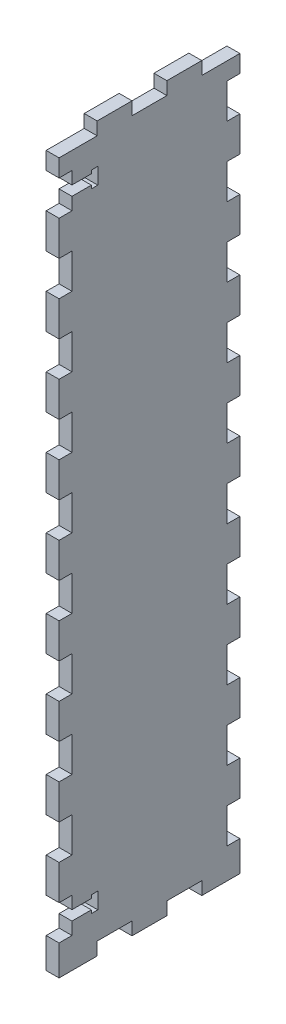
SolidWorks part; units mm, degrees
ref_plane "Front Plane" through (0, 0, 0) normal (0, 0, 1) x (1, 0, 0)
ref_plane "Top Plane" through (0, 0, 0) normal (0, 1, 0) x (1, 0, 0)
ref_plane "Right Plane" through (0, 0, 0) normal (1, 0, 0) x (0, 0, -1)
sketch "Sketch1" plane through (0, 0, 0) normal (1, 0, 0) x (0, 0, -1)
  line L0 (6.35, 355.6) -> (6.35, 349.25) construction
  line L1 (0, 0) -> (88.9, 0) construction
  line L2 (0, 0) -> (0, 6.35) construction
  line L3 (6.35, 355.6) -> (76.2, 355.6) construction
  line L4 (88.9, 0) -> (88.9, 6.35) construction
  line L5 (0, 6.35) -> (88.9, 6.35) construction
  line L6 (6.35, 349.25) -> (88.9, 349.25) construction
  line L7 (82.55, 355.6) -> (82.55, 338.1375) construction
  line L8 (0, 6.35) -> (0, 0)
  line L9 (0, 0) -> (6.35, 0)
  line L10 (6.35, 0) -> (18.7325, 0)
  line L11 (18.7325, 0) -> (18.7325, 6.35)
  line L12 (18.7325, 6.35) -> (35.8775, 6.35)
  line L13 (35.8775, 6.35) -> (35.8775, 0)
  line L14 (35.8775, 0) -> (53.0225, 0)
  line L15 (53.0225, 0) -> (53.0225, 6.35)
  line L16 (53.0225, 6.35) -> (70.1675, 6.35)
  line L17 (70.1675, 6.35) -> (70.1675, 0)
  line L18 (70.1675, 0) -> (82.55, 0)
  line L19 (82.55, 0) -> (88.9, 0)
  line L20 (88.9, 0) -> (88.9, 6.35)
  line L21 (6.35, 12.3825) -> (6.35, 0) construction
  line L22 (0, 0) -> (0, 349.25) construction
  line L23 (0, 6.35) -> (0, 14.9225)
  line L24 (0, 49.2125) -> (6.35, 49.2125)
  line L25 (6.35, 49.2125) -> (6.35, 66.3575)
  line L26 (6.35, 66.3575) -> (0, 66.3575)
  line L27 (0, 66.3575) -> (0, 83.5025)
  line L28 (0, 83.5025) -> (6.35, 83.5025)
  line L29 (6.35, 83.5025) -> (6.35, 100.6475)
  line L30 (6.35, 100.6475) -> (0, 100.6475)
  line L31 (0, 100.6475) -> (0, 117.7925)
  line L32 (0, 117.7925) -> (6.35, 117.7925)
  line L33 (6.35, 117.7925) -> (6.35, 134.9375)
  line L34 (6.35, 134.9375) -> (0, 134.9375)
  line L35 (0, 134.9375) -> (0, 152.0825)
  line L36 (0, 152.0825) -> (6.35, 152.0825)
  line L37 (6.35, 152.0825) -> (6.35, 169.2275)
  line L38 (6.35, 169.2275) -> (0, 169.2275)
  line L39 (0, 169.2275) -> (0, 186.3725)
  line L40 (0, 186.3725) -> (6.35, 186.3725)
  line L41 (6.35, 186.3725) -> (6.35, 203.5175)
  line L42 (6.35, 203.5175) -> (0, 203.5175)
  line L43 (0, 203.5175) -> (0, 220.6625)
  line L44 (0, 220.6625) -> (6.35, 220.6625)
  line L45 (6.35, 220.6625) -> (6.35, 237.8075)
  line L46 (6.35, 237.8075) -> (0, 237.8075)
  line L47 (0, 237.8075) -> (0, 254.9525)
  line L48 (0, 254.9525) -> (6.35, 254.9525)
  line L49 (6.35, 254.9525) -> (6.35, 272.0975)
  line L50 (6.35, 272.0975) -> (0, 272.0975)
  line L51 (0, 272.0975) -> (0, 289.2425)
  line L52 (0, 289.2425) -> (6.35, 289.2425)
  line L53 (6.35, 289.2425) -> (6.35, 306.3875)
  line L54 (6.35, 306.3875) -> (0, 306.3875)
  line L55 (0, 306.3875) -> (0, 323.5325)
  line L56 (0, 323.5325) -> (6.35, 323.5325)
  line L57 (6.35, 323.5325) -> (6.35, 329.692)
  line L58 (6.35, 340.6775) -> (0, 340.6775)
  line L59 (0, 340.6775) -> (0, 349.25)
  line L60 (6.35, 349.25) -> (0, 349.25)
  line L61 (6.35, 334.518) -> (6.35, 340.6775)
  line L62 (6.35, 349.25) -> (18.7325, 349.25)
  line L63 (18.7325, 349.25) -> (18.7325, 355.6)
  line L64 (18.7325, 355.6) -> (35.8775, 355.6)
  line L65 (35.8775, 355.6) -> (35.8775, 349.25)
  line L66 (35.8775, 349.25) -> (53.0225, 349.25)
  line L67 (53.0225, 349.25) -> (53.0225, 355.6)
  line L68 (53.0225, 355.6) -> (70.1675, 355.6)
  line L69 (70.1675, 355.6) -> (70.1675, 349.25)
  line L70 (70.1675, 349.25) -> (88.9, 349.25)
  line L71 (88.9, 6.35) -> (88.9, 14.9225)
  line L72 (88.9, 14.9225) -> (82.55, 14.9225)
  line L73 (82.55, 12.3825) -> (82.55, 0) construction
  line L74 (82.55, 14.9225) -> (82.55, 32.0675)
  line L75 (82.55, 32.0675) -> (88.9, 32.0675)
  line L76 (88.9, 32.0675) -> (88.9, 49.2125)
  line L77 (88.9, 66.3575) -> (88.9, 83.5025)
  line L78 (82.55, 66.3575) -> (88.9, 66.3575)
  line L79 (82.55, 49.2125) -> (82.55, 66.3575)
  line L80 (88.9, 49.2125) -> (82.55, 49.2125)
  line L81 (88.9, 100.6475) -> (88.9, 117.7925)
  line L82 (82.55, 100.6475) -> (88.9, 100.6475)
  line L83 (82.55, 83.5025) -> (82.55, 100.6475)
  line L84 (88.9, 83.5025) -> (82.55, 83.5025)
  line L85 (88.9, 134.9375) -> (88.9, 152.0825)
  line L86 (82.55, 134.9375) -> (88.9, 134.9375)
  line L87 (82.55, 117.7925) -> (82.55, 134.9375)
  line L88 (88.9, 117.7925) -> (82.55, 117.7925)
  line L89 (88.9, 169.2275) -> (88.9, 186.3725)
  line L90 (82.55, 169.2275) -> (88.9, 169.2275)
  line L91 (82.55, 152.0825) -> (82.55, 169.2275)
  line L92 (88.9, 152.0825) -> (82.55, 152.0825)
  line L93 (88.9, 203.5175) -> (88.9, 220.6625)
  line L94 (82.55, 203.5175) -> (88.9, 203.5175)
  line L95 (82.55, 186.3725) -> (82.55, 203.5175)
  line L96 (88.9, 186.3725) -> (82.55, 186.3725)
  line L97 (88.9, 237.8075) -> (88.9, 254.9525)
  line L98 (82.55, 237.8075) -> (88.9, 237.8075)
  line L99 (82.55, 220.6625) -> (82.55, 237.8075)
  line L100 (88.9, 220.6625) -> (82.55, 220.6625)
  line L101 (88.9, 272.0975) -> (88.9, 289.2425)
  line L102 (82.55, 272.0975) -> (88.9, 272.0975)
  line L103 (82.55, 254.9525) -> (82.55, 272.0975)
  line L104 (88.9, 254.9525) -> (82.55, 254.9525)
  line L105 (88.9, 306.3875) -> (88.9, 323.5325)
  line L106 (82.55, 306.3875) -> (88.9, 306.3875)
  line L107 (82.55, 289.2425) -> (82.55, 306.3875)
  line L108 (88.9, 289.2425) -> (82.55, 289.2425)
  line L109 (88.9, 340.6775) -> (88.9, 349.25)
  line L110 (82.55, 340.6775) -> (88.9, 340.6775)
  line L111 (88.9, 6.35) -> (88.9, 0)
  line L112 (82.55, 323.5325) -> (82.55, 340.6775)
  line L113 (0, 46.6725) -> (0, 49.2125) construction
  line L114 (88.9, 323.5325) -> (82.55, 323.5325)
  line L115 (0, 14.9225) -> (6.35, 14.9225)
  line L116 (6.35, 14.9225) -> (6.35, 21.082)
  line L117 (6.35, 32.0675) -> (0, 32.0675)
  line L118 (0, 32.0675) -> (0, 49.2125)
  line L119 (6.35, 332.105) -> (19.05, 332.105) construction
  line L120 (19.05, 328.105) -> (15.875, 328.105)
  line L121 (6.35, 334.518) -> (15.875, 334.518)
  line L122 (15.875, 329.692) -> (15.875, 328.105)
  line L123 (6.35, 329.692) -> (15.875, 329.692)
  line L124 (19.05, 328.105) -> (19.05, 336.105)
  line L125 (19.05, 336.105) -> (15.875, 336.105)
  line L126 (15.875, 334.518) -> (15.875, 336.105)
  line L127 (0, 177.8) -> (88.9237, 177.8) construction
  line L128 (6.35, 25.908) -> (15.875, 25.908)
  line L129 (6.35, 21.082) -> (15.875, 21.082)
  line L130 (19.05, 19.495) -> (15.875, 19.495)
  line L131 (15.875, 21.082) -> (15.875, 19.495)
  line L132 (19.05, 27.495) -> (19.05, 19.495)
  line L133 (19.05, 27.495) -> (15.875, 27.495)
  line L134 (15.875, 25.908) -> (15.875, 27.495)
  line L135 (6.35, 25.908) -> (6.35, 32.0675)
  dimension "D2" = 10
  dimension "D3" = 6.35
  dimension "D4" = 6.35
  dimension "D5" = 6.35
  dimension "D6" = 6.35
  dimension "D7" = 12.3825
  dimension "D8" = 17.145
  dimension "D9" = 17.145
  dimension "D10" = 12.3825
  dimension "D11" = 8.5725
  dimension "D12" = 10
  dimension "D13" = 4
  dimension "D14" = 3.175
  dimension "D15" = 9.525
  dimension "D16" = 2.413
  dimension "D17" = 6.35
  dimension "D18" = 17.145
  dimension "D19" = 12.3825
  dimension "D20" = 17.145
  dimension "D21" = 17.145
  dimension "D22" = 17.145
  dimension "D23" = 18.7325
extrude "Boss-Extrude1" add sketch "Sketch1" along normal blind 6.35 contours L111 L107 L103 L95 L83 L78 L70 L69 L68 L67 L66 L65 L64 L63 L62 region at (0, 177.0157, -44.6044)
